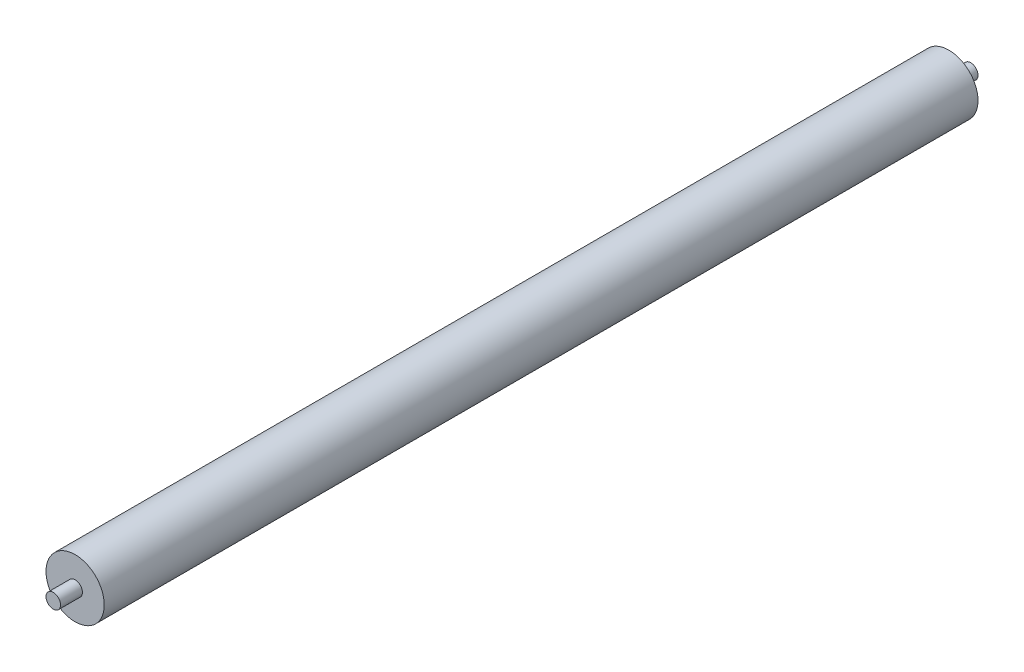
SolidWorks part; units mm, degrees
material "AISI 1035 Steel (SS)"
ref_plane "Front Plane" through (0, 0, 0) normal (0, 0, 1) x (1, 0, 0)
ref_plane "Top Plane" through (0, 0, 0) normal (0, 1, 0) x (1, 0, 0)
ref_plane "Right Plane" through (0, 0, 0) normal (1, 0, 0) x (0, 0, -1)
sketch "Sketch1" plane through (0, 0, 0) normal (0, 0, 1) x (1, 0, 0)
  circle A0 centre (0, 0) radius 25.4
  circle A1 centre (0, 0) radius 6.35
  dimension "D1" = 50.8
  dimension "D2" = 12.7
extrude "Boss-Extrude1" add sketch "Sketch1" along normal mid plane 800.1 contours A1 region at (0, 0, 0)
extrude "Boss-Extrude2" add sketch "Sketch1<3>" along normal mid plane 762
sketch "Sketch1<3>" plane through (0, 0, 0) normal (0, 0, 1) x (1, 0, 0) same geometry as "Sketch1"
sketch "Sketch2" plane through (0, 0, 0) normal (1, 0, 0) x (0, 0, -1)
  circle A0 centre (-129.0159, 11.7601) radius 15.13
